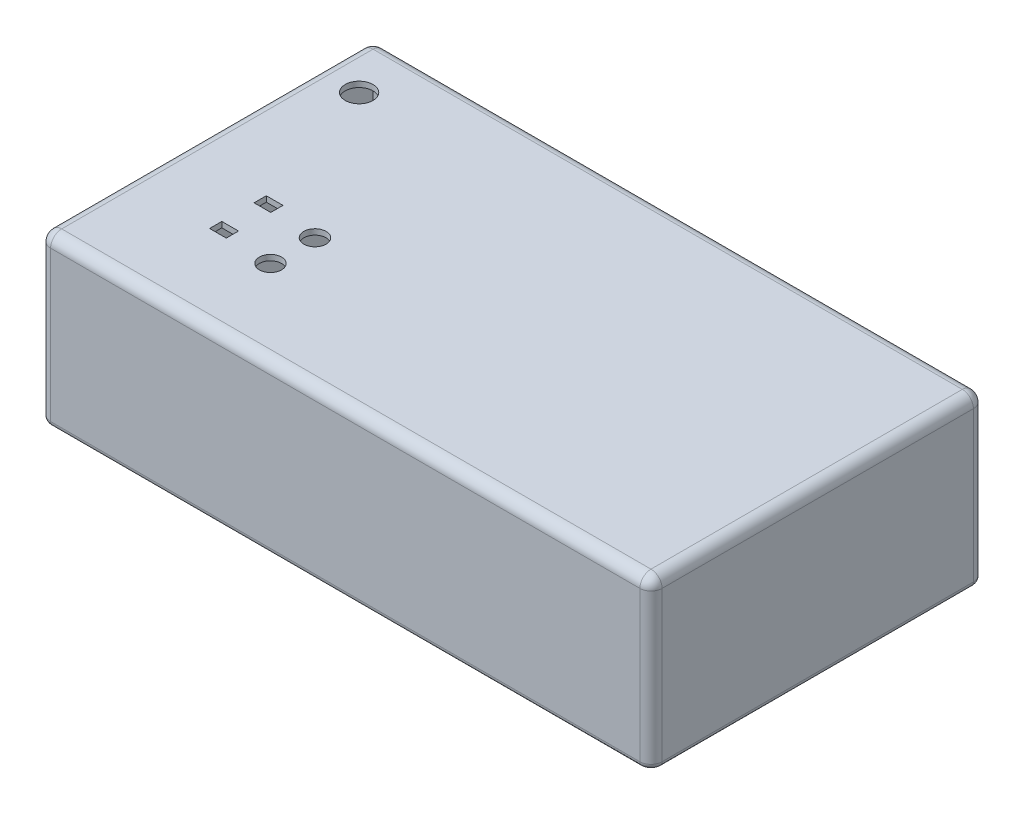
SolidWorks part; units mm, degrees
ref_plane "Front Plane" through (0, 0, 0) normal (0, 0, 1) x (1, 0, 0)
ref_plane "Top Plane" through (0, 0, 0) normal (0, 1, 0) x (1, 0, 0)
ref_plane "Right Plane" through (0, 0, 0) normal (1, 0, 0) x (0, 0, -1)
sketch "Sketch1" plane through (0, 0, 0) normal (0, 1, 0) x (1, 0, 0)
  line L1 (-55, -30) -> (55, -30)
  line L2 (-55, -30) -> (-55, 30)
  line L3 (-55, 30) -> (55, 30)
  line L4 (55, -30) -> (55, 30)
  line L5 (-55, -30) -> (55, 30) construction
  line L6 (-55, 30) -> (55, -30) construction
  point P0 (0, 0)
  dimension "D1" = 110
  dimension "D2" = 60
extrude "Boss-Extrude1" add sketch "Sketch1" along normal blind 30
sketch "Sketch2" plane through (0, 0, 0) normal (0, -1, 0) x (1, 0, 0)
  line L0 (-55, -30) -> (-55, 30) construction
  line L1 (-54, -29) -> (54, -29)
  line L2 (-54, -29) -> (-54, 29)
  line L3 (-54, 29) -> (54, 29)
  line L4 (54, -29) -> (54, 29)
  line L5 (-54, -29) -> (54, 29) construction
  line L6 (-54, 29) -> (54, -29) construction
  line L8 (-55, 30) -> (55, 30) construction
  point P0 (0, 0)
  dimension "D1" = 1
  dimension "D2" = 1
extrude "Cut-Extrude1" cut sketch "Sketch2" against normal blind 29
fillet "Fillet1" radius 2 4 edges at (55, 30, 0) (0, 30, -30) (-55, 30, 0) (0, 30, 30)
fillet "Fillet2" radius 2 8 edges at (54.4142, 29.4142, -29.4142) (54.4142, 29.4142, 29.4142) (-54.4142, 29.4142, -29.4142) (-54.4142, 29.4142, 29.4142) (55, 14, -30) (55, 14, 30) (-55, 14, -30) (-55, 14, 30)
sketch "Sketch6" plane through (0, 30, 0) normal (0, 1, 0) x (1, 0, 0)
  circle A0 centre (-28.8384, -14.6077) radius 2
  circle A1 centre (-28.8384, -6.6077) radius 2
extrude "Cut-Extrude2" cut sketch "Sketch6" against normal blind 10
sketch "Sketch7" plane through (0, 30, 0) normal (0, 1, 0) x (1, 0, 0)
  line L0 (-39.7634, -4.4327) -> (-36.7634, -4.4327)
  line L1 (-39.7634, -4.4327) -> (-39.7634, -6.6327)
  line L2 (-39.7634, -6.6327) -> (-36.7634, -6.6327)
  line L3 (-36.7634, -4.4327) -> (-36.7634, -6.6327)
  line L4 (-39.7634, -4.4327) -> (-36.7634, -6.6327) construction
  line L5 (-39.7634, -6.6327) -> (-36.7634, -4.4327) construction
  line L6 (-39.7634, -12.4327) -> (-36.7634, -12.4327)
  line L7 (-39.7634, -12.4327) -> (-39.7634, -14.6327)
  line L8 (-39.7634, -14.6327) -> (-36.7634, -14.6327)
  line L9 (-36.7634, -12.4327) -> (-36.7634, -14.6327)
  line L10 (-39.7634, -12.4327) -> (-36.7634, -14.6327) construction
  line L11 (-39.7634, -14.6327) -> (-36.7634, -12.4327) construction
  circle A0 centre (-28.8384, -14.6077) radius 2 construction
  point P0 (-38.2634, -5.5327)
  point P5 (-38.2634, -13.5327)
  dimension "D1" = 8
  dimension "D2" = 9.425
  dimension "D3" = 1.075
extrude "Cut-Extrude3" cut sketch "Sketch7" against normal blind 10
sketch "Sketch8" plane through (0, 30, 0) normal (0, 1, 0) x (1, 0, 0)
  line L0 (-53, 30) -> (53, 30) construction
  line L2 (-55, -28) -> (-55, 28) construction
  circle A0 centre (-47.5, 20) radius 2.5
  point P4 (0, 0)
  dimension "D1" = 5
  dimension "D2" = 10
  dimension "D3" = 7.5
extrude "Cut-Extrude4" cut sketch "Sketch8" against normal blind 10
fillet "Fillet5" radius 1 8 edges at (-54.4142, 0, 29.4142) (-54.4142, 0, -29.4142) (54.4142, 0, -29.4142) (54.4142, 0, 29.4142) (-55, 0, 0) (0, 0, -30) (55, 0, 0) (0, 0, 30)
fillet "Fillet6" radius 1 4 edges at (-54, 29, 0) (0, 29, -29) (0, 29, 29) (54, 29, 0)
